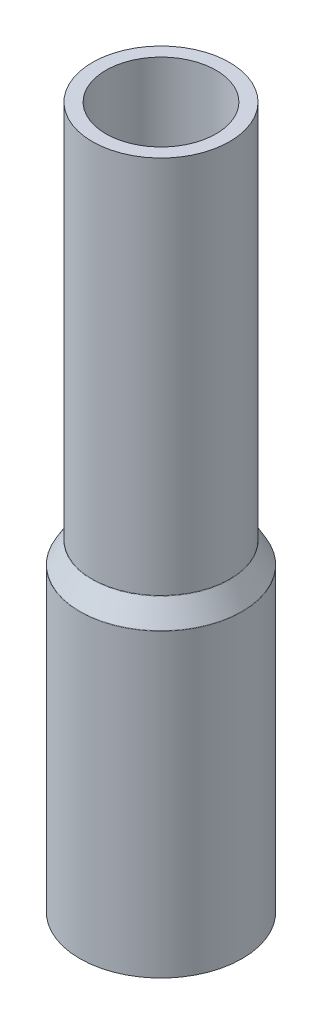
SolidWorks part; units mm, degrees
material "PE High Density"
ref_plane "Front Plane" through (0, 0, 0) normal (0, 0, 1) x (1, 0, 0)
ref_plane "Top Plane" through (0, 0, 0) normal (0, 1, 0) x (1, 0, 0)
ref_plane "Right Plane" through (0, 0, 0) normal (1, 0, 0) x (0, 0, -1)
sketch "Sketch1" plane through (0, 0, 0) normal (0, 1, 0) x (1, 0, 0)
  circle A0 centre (0, 0) radius 0.81
  circle A1 centre (0, 0) radius 0.685
  dimension "D1" = 1.62
  dimension "D2" = 1.37
extrude "Boss-Extrude1" add sketch "Sketch1" along normal blind 3
sketch "Sketch2" plane through (0, 3, 0) normal (0, 1, 0) x (1, 0, 0)
  circle A0 centre (0, 0) radius 0.55
  circle A1 centre (0, 0) radius 0.685
  circle A2 centre (0, 0) radius 0.685 construction
  dimension "D1" = 1.1
extrude "Boss-Extrude2" add sketch "Sketch2" along normal blind 4 separate body
sketch "Sketch3" plane through (0, 0, 0) normal (0, 0, 1) x (1, 0, 0)
  line L0 (0, 0) -> (0, 8.1367) construction
  line L1 (-0.81, 3) -> (-0.685, 3.2165)
  line L2 (-0.685, 7) -> (-0.685, 3) construction
  line L3 (-0.685, 3.2165) -> (-0.685, 3)
  line L4 (0.81, 3) -> (-0.81, 3) construction
  line L5 (-0.685, 3) -> (-0.81, 3)
  dimension "D1" = 60
revolve "Revolve1" add sketch "Sketch3" angle 360 about L0
fillet "Fillet1" radius 0.01 1 edges at (0, 3, 0.81)
fillet "Fillet2" radius 0.01 1 edges at (0, 3.2165, -0.685)
ref_plane "Plane1" through (0, 0, 0.55) normal (0, 0, 1) x (1, 0, 0)
sketch "Sketch4" plane through (0, 0, 0.55) normal (0, 0, 1) x (1, 0, 0)
  line L0 (0, 0) -> (0, 7) construction
  line L1 (-0.685, 0) -> (0.685, 0) construction
  line L2 (0.55, 7) -> (-0.55, 7) construction
ref_axis "Axis1" through (0, 7, 0) along (0, -1, 0)
